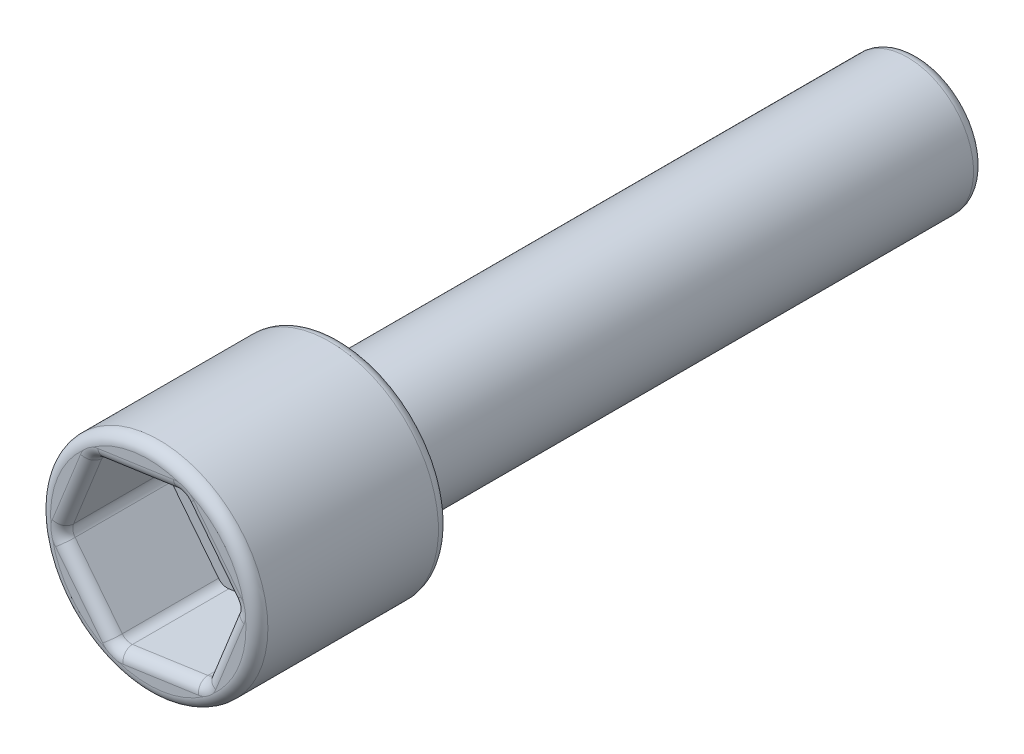
SolidWorks part; units mm, degrees
ref_plane "Front Plane" through (0, 0, 0) normal (0, 0, 1) x (1, 0, 0)
ref_plane "Top Plane" through (0, 0, 0) normal (0, 1, 0) x (1, 0, 0)
ref_plane "Right Plane" through (0, 0, 0) normal (1, 0, 0) x (0, 0, -1)
sketch "Sketch1" plane through (0, 0, 0) normal (0, 0, 1) x (1, 0, 0)
  circle A0 centre (0, 0) radius 5.0165
  dimension "D1" = 10.033
extrude "Boss-Extrude1" add sketch "Sketch1" along normal blind 5.08
sketch "Sketch3" plane through (0, 0, 0) normal (0, 0, -1) x (-1, 0, 0)
  circle A0 centre (0, 0) radius 5.0165
extrude "Boss-Extrude2" add sketch "Sketch3" along normal blind 3.81
sketch "Sketch5" plane through (0, 0, -3.81) normal (0, 0, -1) x (-1, 0, 0)
  circle A0 centre (0, 0) radius 3.048
  dimension "D1" = 6.096
extrude "Boss-Extrude3" add sketch "Sketch5" along normal blind 26.67
sketch "Sketch6" plane through (0, 0, -30.48) normal (0, 0, -1) x (-1, 0, 0)
  circle A0 centre (0, 0) radius 1.651
  dimension "D1" = 3.302
extrude "Cut-Extrude3" cut sketch "Sketch6" against normal through all
sketch "Sketch8" plane through (0, 0, 5.08) normal (0, 0, 1) x (1, 0, 0)
  line L1 (1.524, 3.8128) -> (-2.54, 3.2262)
  line L2 (-2.54, 3.2262) -> (-4.064, -0.5866)
  line L3 (-4.064, -0.5866) -> (-1.524, -3.8128)
  line L4 (-1.524, -3.8128) -> (2.54, -3.2262)
  line L5 (2.54, -3.2262) -> (4.064, 0.5866)
  line L6 (4.064, 0.5866) -> (1.524, 3.8128)
  circle A0 centre (0, 0) radius 3.556 construction
  point P1 (-0.508, 3.5195)
  dimension "D1" = 7.112
  dimension "D2" = 8.128
extrude "Cut-Extrude4" cut sketch "Sketch8" against normal blind 4.953
fillet "Fillet1" radius 0.508 18 edges at (5.0165, 0, 5.08) (-1.524, -3.8128, 2.6035) (4.064, 0.5866, 2.6035) (2.54, -3.2262, 2.6035) (1.524, 3.8128, 2.6035) (-2.54, 3.2262, 2.6035) (-4.064, -0.5866, 2.6035) (-1.651, 0, -30.48) (-3.048, 0, -3.81) (-3.048, 0, -30.48) (-5.0165, 0, -3.81) (1.651, 0, 0.127) (-3.302, 1.3198, 5.08) (3.302, -1.3198, 5.08) (-0.508, 3.5195, 5.08) (2.794, 2.1997, 5.08) (-2.794, -2.1997, 5.08) (0.508, -3.5195, 5.08)
